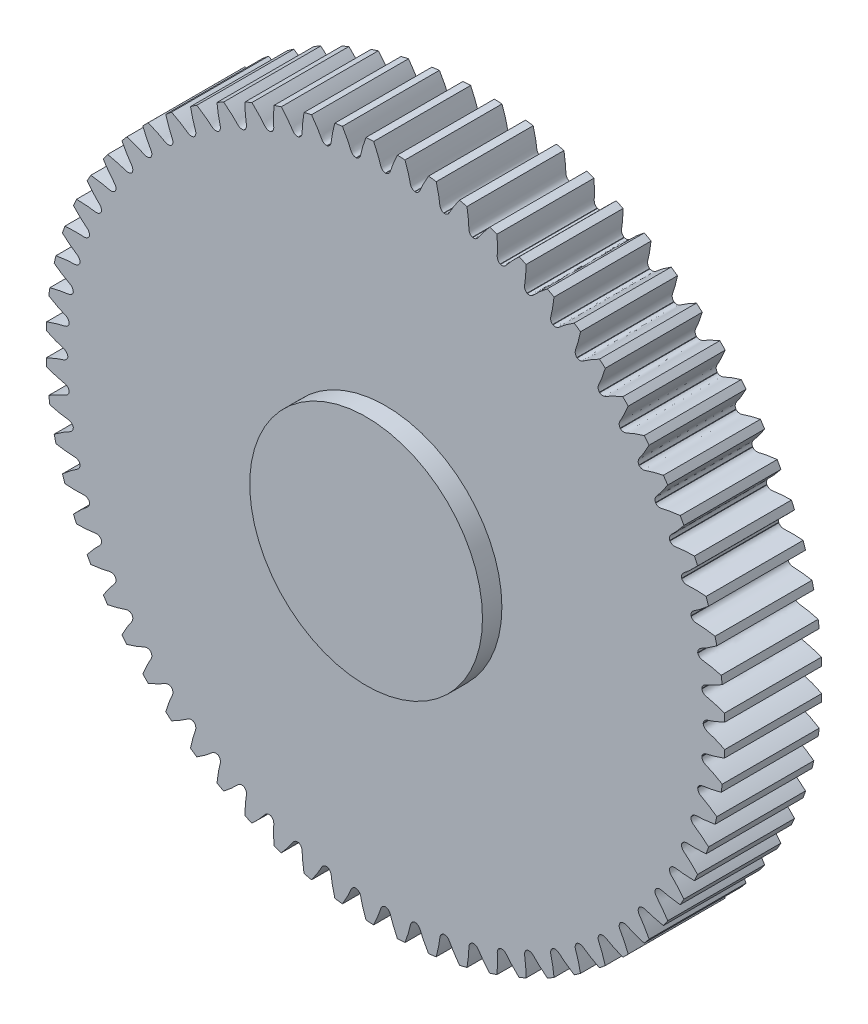
SolidWorks part; units mm, degrees
ref_plane "前视基准面" through (0, 0, 0) normal (0, 0, 1) x (1, 0, 0)
ref_plane "上视基准面" through (0, 0, 0) normal (0, 1, 0) x (1, 0, 0)
ref_plane "右视基准面" through (0, 0, 0) normal (1, 0, 0) x (0, 0, -1)
sketch "草图1" plane through (0, 0, 0) normal (0, 0, 1) x (1, 0, 0)
  circle A0 centre (0, 0) radius 17.5
extrude "凸台-拉伸1" add sketch "草图1" along normal blind 5
ref_axis "基准轴1" through (0, 0, 5) along (0, 0, -1)
sketch "草图2" plane through (0, 0, 0) normal (0, 0, 1) x (1, 0, 0)
  line L0 (0, 0) -> (0, 17.5) construction
  circle A0 centre (0, 0) radius 17.5 construction
  arc A1 (0.01, 16.3749) -> (-0.01, 16.3749) centre (0, 0) ccw
  arc A2 (2.2668, 19.8177) -> (-2.2668, 19.8177) centre (0, 0) ccw
  spline S0 degree 3 poles (0.01, 16.3749) (0.2151, 16.4199) (0.2524, 16.6031) (0.3238, 16.8098) (0.3602, 16.9114) (0.4012, 17.0181) (0.4466, 17.1299) (0.4969, 17.2467) (0.552, 17.3682) (0.6124, 17.4944) (0.6781, 17.625) (0.7495, 17.76) (0.8266, 17.8991) (0.9096, 18.0422) (0.9989, 18.189) (1.0945, 18.3394) (1.1966, 18.4932) (1.3054, 18.6501) (1.421, 18.8101) (1.5437, 18.9728) (1.6736, 19.138) (1.8108, 19.3056) (2.0064, 19.535) (2.1605, 19.7049) (2.2668, 19.8177) knots 0 0 0 0 0.107618 0.13204 0.158 0.185496 0.21453 0.245101 0.277209 0.310855 0.346037 0.382757 0.421014 0.460808 0.50214 0.545008 0.589414 0.635357 0.682837 0.731855 0.782409 0.834501 0.88813 1 1 1 1
  spline S1 degree 3 poles (-0.01, 16.3749) (-0.2151, 16.4199) (-0.2524, 16.6031) (-0.3238, 16.8098) (-0.3602, 16.9114) (-0.4012, 17.0181) (-0.4466, 17.1299) (-0.4969, 17.2467) (-0.552, 17.3682) (-0.6124, 17.4944) (-0.6781, 17.625) (-0.7495, 17.76) (-0.8266, 17.8991) (-0.9096, 18.0422) (-0.9989, 18.189) (-1.0945, 18.3394) (-1.1966, 18.4932) (-1.3054, 18.6501) (-1.421, 18.8101) (-1.5437, 18.9728) (-1.6736, 19.138) (-1.8108, 19.3056) (-2.0064, 19.535) (-2.1605, 19.7049) (-2.2668, 19.8177) knots 0 0 0 0 0.107618 0.13204 0.158 0.185496 0.21453 0.245101 0.277209 0.310855 0.346037 0.382757 0.421014 0.460808 0.50214 0.545008 0.589414 0.635357 0.682837 0.731855 0.782409 0.834501 0.88813 1 1 1 1
extrude "切除-拉伸1" cut sketch "草图2" along normal through all
pattern_circular "阵列(圆周)1" count 68 every 5.294 about axis through (0, 0, 5) along (0, 0, -1) of "切除-拉伸1"
sketch "草图3" plane through (0, 0, 0) normal (0, 0, 1) x (1, 0, 0)
  circle A0 centre (0, 0) radius 17 construction
  dimension "Dn" = 34
sketch "草图4" plane through (0, 0, 5) normal (0, 0, 1) x (1, 0, 0)
  circle A0 centre (0, 0) radius 6
  dimension "D1" = 12
extrude "凸台-拉伸2" add sketch "草图4" along normal blind 1
